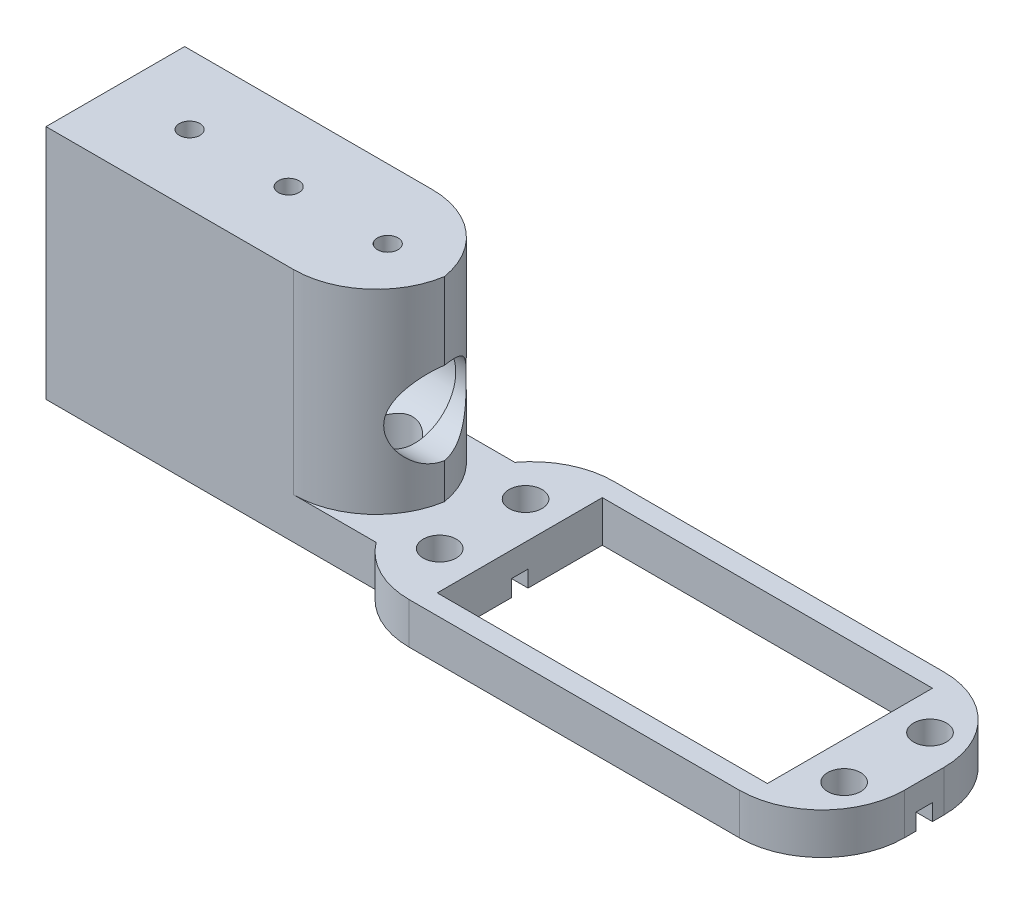
SolidWorks part; units mm, degrees
ref_plane "Front Plane" through (0, 0, 0) normal (0, 0, 1) x (1, 0, 0)
ref_plane "Top Plane" through (0, 0, 0) normal (0, 1, 0) x (1, 0, 0)
ref_plane "Right Plane" through (0, 0, 0) normal (1, 0, 0) x (0, 0, -1)
sketch "Sketch1" plane through (0, 0, 0) normal (0, 1, 0) x (1, 0, 0)
  line L0 (0, 0) -> (-9, 0)
  line L1 (0, 0) -> (40, 0)
  line L2 (0, 0) -> (0, -20)
  line L3 (0, -20) -> (40, -20)
  line L4 (40, 0) -> (40, -20)
  line L5 (-9, 0) -> (-9, 2.4)
  line L6 (-9, 2.4) -> (49, 2.4)
  line L7 (49, 2.4) -> (49, -22.4)
  line L8 (49, -22.4) -> (-9, -22.4)
  line L9 (-9, -22.4) -> (-9, 0)
  line L10 (0, -10) -> (0, -4.8)
  line L11 (0, -4.8) -> (-4.5, -4.8)
  line L12 (0, -10) -> (40, -10)
  line L13 (20, 0) -> (20, -20)
  circle A0 centre (-4.5, -4.8) radius 2
  circle A1 centre (44.5, -4.8) radius 2
  circle A2 centre (44.5, -15.2) radius 2
  circle A3 centre (-4.5, -15.2) radius 2
  dimension "D1" = 40
  dimension "D2" = 20
extrude "Boss-Extrude1" add sketch "Sketch1" along normal blind 5
sketch "Sketch2" plane through (-9, 0, 0) normal (-1, 0, 0) x (0, 0, 1)
  line L0 (22.4, 0) -> (-2.4, 0) construction
  line L1 (9, -2) -> (11, -2)
  line L2 (9, -2) -> (9, 2)
  line L3 (9, 2) -> (11, 2)
  line L4 (11, -2) -> (11, 2)
  line L5 (9, -2) -> (11, 2) construction
  line L6 (9, 2) -> (11, -2) construction
  point P0 (10, 0)
  dimension "D1" = 4
  dimension "D2" = 2
extrude "Cut-Extrude1" cut sketch "Sketch2" against normal through all
sketch "Sketch3" plane through (0, 0, 0) normal (0, -1, 0) x (1, 0, 0)
  line L0 (-9, 10) -> (-9, 18.4)
  line L1 (-9, 11) -> (-9, 9) construction
  line L2 (-9, 22.4) -> (-9, 11) construction
  line L3 (-9, 10) -> (-9, 1.6)
  line L4 (-9, 9) -> (-9, -2.4) construction
  line L5 (-9, 18.4) -> (-9, 1.6)
  line L6 (-9, 18.4) -> (-49, 18.4)
  line L7 (-9, 1.6) -> (-49, 1.6)
  line L8 (-49, 18.4) -> (-49, 1.6)
  line M4 (-9, 22.4) -> (-9, 11)
  dimension "D1" = 40
  dimension "D2" = 16.8
extrude "Boss-Extrude2" add sketch "Sketch3" against normal blind 28.625 contours L6 L8 L7 L3 L0 M4
fillet "Fillet1" radius 10 4 edges at (-9, 2.5, 22.4) (-9, 2.5, -2.4) (49, 2.5, -2.4) (49, 2.5, 22.4)
sketch "Sketch4" plane through (-49, 0, 0) normal (-1, 0, 0) x (0, 0, 1)
  line L0 (1.6, 28.625) -> (18.4, 0)
  circle A0 centre (10, 14.3125) radius 6.1
extrude "Cut-Extrude2" cut sketch "Sketch4" against normal blind 36.25 contours L0 A0 | L0 A0
sketch "Sketch5" plane through (-12.75, 0, 0) normal (-1, 0, 0) x (0, 0, 1)
  circle A0 centre (10, 14.3125) radius 5
extrude "Cut-Extrude3" cut sketch "Sketch5" against normal up to next
fillet "Fillet4" radius 10 2 edges at (-9, 16.8125, 1.6) (-9, 16.8125, 18.4)
sketch "Sketch8" plane through (0, 0, 0) normal (0, -1, 0) x (1, 0, 0)
  line L0 (-49, 10) -> (-40, 10)
  line L1 (-49, 18.4) -> (-49, 1.6) construction
  line L2 (-40, 10) -> (-28, 10)
  line L3 (-28, 10) -> (-16, 10)
  circle A0 centre (-40, 10) radius 3
  circle A1 centre (-28, 10) radius 3
  circle A2 centre (-16, 10) radius 3
extrude "Cut-Extrude6" cut sketch "Sketch8" against normal blind 22
sketch "Sketch9" plane through (0, 22, 0) normal (0, -1, 0) x (1, 0, 0)
  circle A0 centre (-40, 10) radius 1.25
  circle A1 centre (-28, 10) radius 1.25
  circle A2 centre (-16, 10) radius 1.25
extrude "Cut-Extrude7" cut sketch "Sketch9" against normal through all
fillet "Fillet5" radius 2 1 edges at (-49, 14.3125, 16.1)
